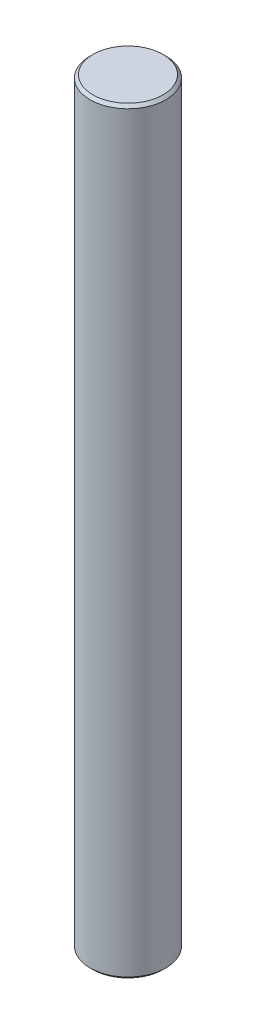
SolidWorks part; units mm, degrees
material "Ductile Iron (SN)"
ref_plane "Front Plane" through (0, 0, 0) normal (0, 0, 1) x (1, 0, 0)
ref_plane "Top Plane" through (0, 0, 0) normal (0, 1, 0) x (1, 0, 0)
ref_plane "Right Plane" through (0, 0, 0) normal (1, 0, 0) x (0, 0, -1)
sketch "Sketch1" plane through (0, 0, 0) normal (0, 1, 0) x (1, 0, 0)
  circle A0 centre (0, 0) radius 2
  dimension "D1" = 4
extrude "Boss-Extrude1" add sketch "Sketch1" along normal blind 40
chamfer "Chamfer1" distance 0.15 angle 45 2 edges at (0, 0, 2) (0, 40, 2)
